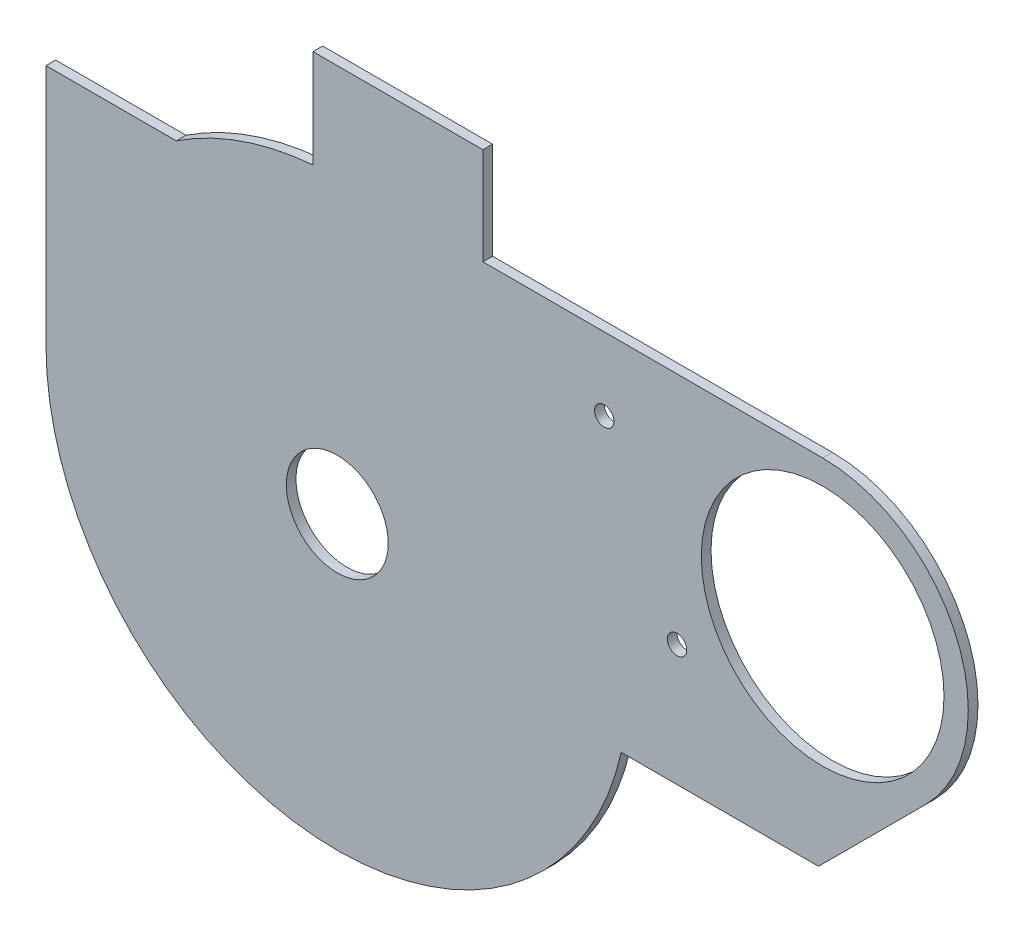
SolidWorks part; units mm, degrees
ref_plane "前视基准面" through (0, 0, 0) normal (0, 0, 1) x (1, 0, 0)
ref_plane "上视基准面" through (0, 0, 0) normal (0, 1, 0) x (1, 0, 0)
ref_plane "右视基准面" through (0, 0, 0) normal (1, 0, 0) x (0, 0, -1)
sketch "Sketch1" plane through (0, 0, 0) normal (0, 0, 1) x (1, 0, 0)
  line L0 (-26.5591, 60) -> (97.717, 60) construction
  line L3 (-33.1662, 50) -> (-60, 50)
  line L4 (-60, 0) -> (-60, 50)
  line L5 (100, 60) -> (0, 60)
  line L6 (73.5456, -38.8808) -> (87.301, -25.1254) construction
  line L7 (106.8791, 60) -> (171.5951, 60) construction
  line L10 (99.1522, -13.2742) -> (121.2132, 8.7868)
  line L11 (58.5132, -13.2742) -> (99.1522, -13.2742)
  arc A0 (0, 60) -> (58.5132, -13.2742) centre (0, 0) ccw
  circle A2 centre (0, 0) radius 10.5
  arc A4 (121.2132, 8.7868) -> (100, 60) centre (100, 30) ccw
  circle A7 centre (100, 30) radius 25
  dimension "D1" = 120
  dimension "D2" = 100
  dimension "D3" = 21
  dimension "D5" = 60
extrude "Boss-Extrude1" add sketch "Sketch1" along normal blind 2 contours A0 L3 L4 | L5 A0 A4 A2 region at (-52.3919, 38.1269, 0) region at (17.1631, 6.163, 0)
sketch "Sketch2" plane through (0, 0, 2) normal (0, 0, 1) x (1, 0, 0)
  line L0 (100, 60) -> (0, 60) construction
  line L1 (-60, 0) -> (-60, 50) construction
  line L5 (125, 30) -> (100, 5) construction
  line L6 (115.7514, 14.2486) -> (82.3223, 47.6777) construction
  line L7 (58.5132, -13.2742) -> (99.1522, -13.2742) construction
  circle A1 centre (0, 0) radius 57
  circle A2 centre (55, 45) radius 2
  circle A3 centre (70, 11.7258) radius 2
  circle A4 centre (96.4645, 33.5355) radius 15
  circle A5 centre (100, 30) radius 25 construction
  dimension "D1" = 15
  dimension "D4" = 130
  dimension "D5" = 20
  dimension "D2" = 115
  dimension "D3" = 25
extrude "Cut-Extrude1" cut sketch "Sketch2" against normal up to next contours A2 | A3
sketch "Sketch3" plane through (0, 0, 0) normal (0, 0, -1) x (-1, 0, 0)
  line L0 (-30, 18.0278) -> (-30, 80)
  line L1 (-30, 80) -> (5, 80)
  line L2 (5, 80) -> (5, 48)
  line L3 (5, 48) -> (15.6215, 31.3204)
  line L4 (-30, 60) -> (0, 60)
  line L5 (-100, 60) -> (0, 60) construction
  arc A1 (15.6215, 31.3204) -> (-30, 18.0278) centre (0, 0) ccw
  arc A2 (33.1662, 50) -> (0, 60) centre (0, 0) ccw construction
  arc A3 (5, 59.7913) -> (0, 60) centre (0, 0) ccw
  arc M10 (33.1662, 50) -> (0, 60) centre (0, 0) ccw
  line M11 (0, 60) -> (-100, 60)
extrude "Boss-Extrude2" add sketch "Sketch3" against normal blind 2 contours L2 L1 L0 M11 M10 region at (12.4919, 69.995, 0)
sketch "Sketch4" plane through (0, 0, 0) normal (0, 0, -1) x (-1, 0, 0)
  line L0 (-30, 80) -> (5, 80) construction
  line L1 (5, 80) -> (5, 48) construction
  line L3 (-20, 65.5961) -> (-5, 65.5961)
  line L4 (-20, 65.5961) -> (-20, 63.5961)
  line L5 (-20, 63.5961) -> (-5, 63.5961)
  line L6 (-5, 65.5961) -> (-5, 63.5961)
  line L7 (-20, 65.5961) -> (-5, 63.5961) construction
  line L8 (-20, 63.5961) -> (-5, 65.5961) construction
  line L9 (-13.5, 72.0961) -> (-11.5, 72.0961)
  line L10 (-13.5, 72.0961) -> (-13.5, 57.0961)
  line L11 (-13.5, 57.0961) -> (-11.5, 57.0961)
  line L12 (-11.5, 72.0961) -> (-11.5, 57.0961)
  line L13 (-13.5, 72.0961) -> (-11.5, 57.0961) construction
  line L14 (-13.5, 57.0961) -> (-11.5, 72.0961) construction
  point P5 (-12.5, 64.5961)
  point P10 (-12.5, 80)
  point P11 (-12.5, 64.5961)
  dimension "D1" = 15
  dimension "D2" = 2
  dimension "D3" = 0
  dimension "D4" = 15
  dimension "D5" = 2
extrude "Boss-Extrude3" add sketch "Sketch4" along normal blind 1 contours L12 L9 L10 L3 | L10 L3 L4 L5 | L12 L3 L10 L5 | L3 L12 L5 L6 | L12 L5 L10 L11 region at (16.75, 64.5961, 0) region at (12.5, 68.8461, 0) region at (12.5, 64.5961, 0) region at (8.25, 64.5961, 0) region at (12.5, 60.3461, 0)
